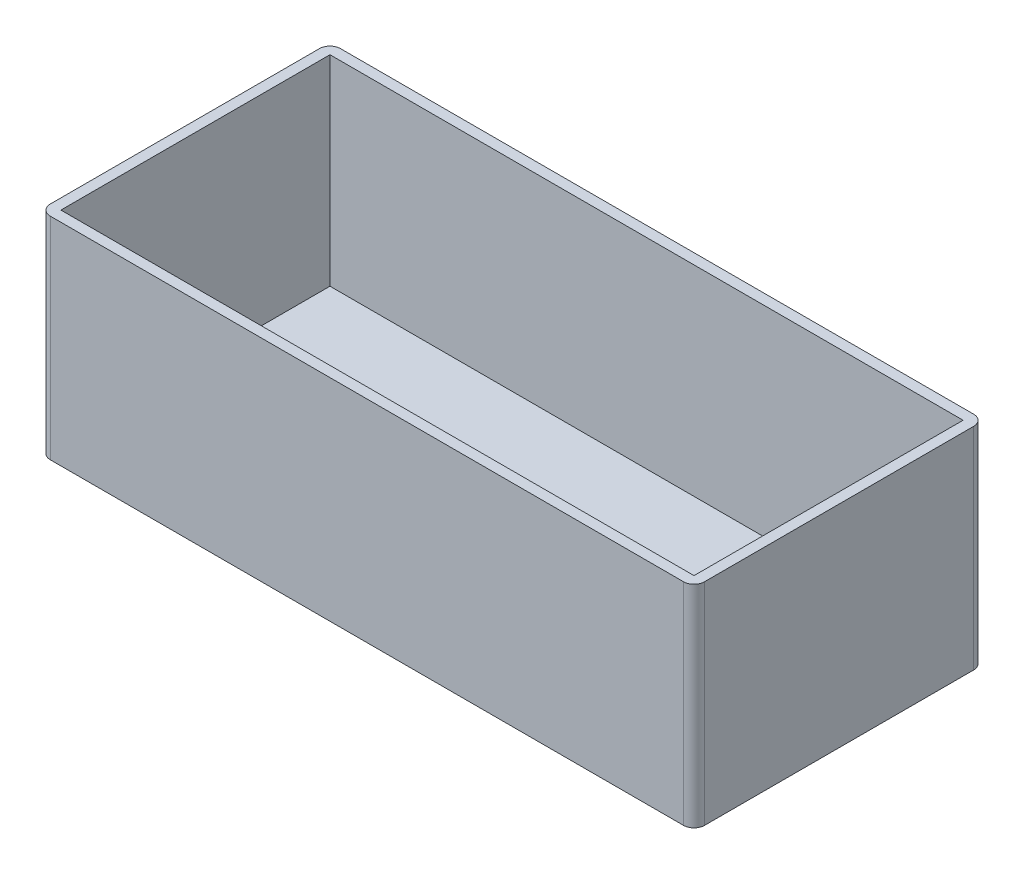
SolidWorks part; units mm, degrees
ref_plane "Front Plane" through (0, 0, 0) normal (0, 0, 1) x (1, 0, 0)
ref_plane "Top Plane" through (0, 0, 0) normal (0, 1, 0) x (1, 0, 0)
ref_plane "Right Plane" through (0, 0, 0) normal (1, 0, 0) x (0, 0, -1)
sketch "Sketch1" plane through (0, 0, 0) normal (0, 1, 0) x (1, 0, 0)
  line L1 (2, 0) -> (122, 0)
  line L2 (0, 2) -> (0, 53)
  line L3 (2, 55) -> (122, 55)
  line L4 (124, 2) -> (124, 53)
  arc A0 (0, 2) -> (2, 0) centre (2, 2) ccw
  arc A1 (122, 0) -> (124, 2) centre (122, 2) ccw
  arc A2 (122, 55) -> (124, 53) centre (122, 53) cw
  arc A3 (2, 55) -> (0, 53) centre (2, 53) ccw
  point P7 (0, 0)
  dimension "D1" = 2
extrude "Boss-Extrude1" add sketch "Sketch1" along normal blind 40 contours L3 A2 L4 A1 L1 A0 L2 A3
shell "Shell1" thickness 2 removed face at (62, 40, -27.5)
